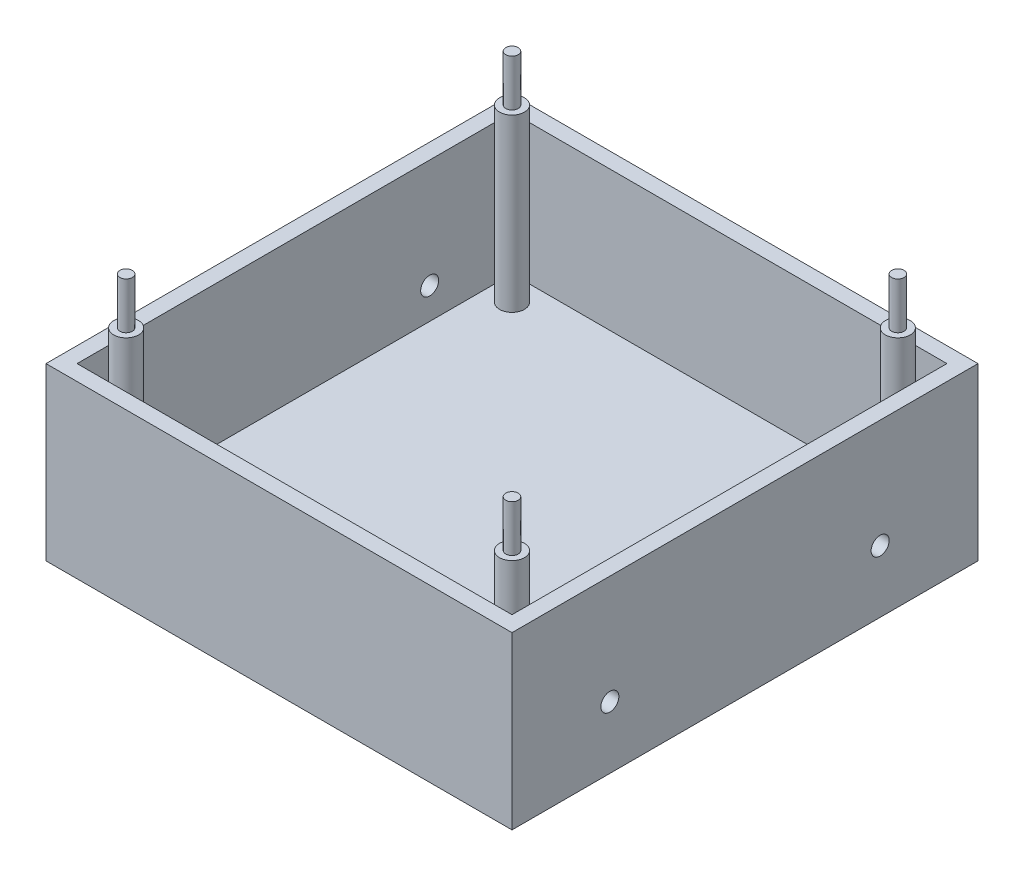
SolidWorks part; units mm, degrees
ref_plane "Front Plane" through (0, 0, 0) normal (0, 0, 1) x (1, 0, 0)
ref_plane "Top Plane" through (0, 0, 0) normal (0, 1, 0) x (1, 0, 0)
ref_plane "Right Plane" through (0, 0, 0) normal (1, 0, 0) x (0, 0, -1)
sketch "Sketch1" plane through (0, 0, 0) normal (0, 1, 0) x (1, 0, 0)
  line L0 (75, 0) -> (75, -156.3817) construction
  line L1 (0, 0) -> (150, 0)
  line L2 (0, 0) -> (0, -150)
  line L3 (0, -150) -> (150, -150)
  line L4 (150, 0) -> (150, -150)
  line L5 (0, -75) -> (163.2244, -75) construction
  line L7 (5, -5) -> (145, -5)
  line L8 (5, -5) -> (5, -145)
  line L9 (5, -145) -> (145, -145)
  line L10 (145, -5) -> (145, -145)
  line L11 (5, -5) -> (145, -145) construction
  line L12 (5, -145) -> (145, -5) construction
  circle A0 centre (12.9, -12.9) radius 4
  circle A1 centre (12.9, -12.9) radius 2
  circle A2 centre (137.1, -12.9) radius 2
  circle A3 centre (137.1, -12.9) radius 4
  circle A4 centre (137.1, -137.1) radius 2
  circle A5 centre (137.1, -137.1) radius 4
  circle A6 centre (12.9, -137.1) radius 2
  circle A7 centre (12.9, -137.1) radius 4
  point P9 (75, -75)
  point P29 (75, -75)
  dimension "D5" = 8
  dimension "D6" = 4
  dimension "D1" = 150
  dimension "D2" = 150
  dimension "D3" = 140
  dimension "D4" = 140
  dimension "D7" = 12.9
  dimension "D9" = 12.9
  dimension "D10" = 12.9
  dimension "D8" = 4
extrude "Boss-Extrude1" add sketch "Sketch1" along normal blind 55 contours L4 L1 L2 L3 L7 L10 L9 L8 region at (75, 0, 2.1213)
extrude "Boss-Extrude2" add sketch "Sketch1<3>" along normal blind 10 contours L10 L7 L8 L9 A7 A5 A3 A0 region at (75, 0, 75)
sketch "Sketch1<3>" plane through (0, 0, 0) normal (0, 1, 0) x (1, 0, 0) same geometry as "Sketch1"
extrude "Boss-Extrude3" add sketch "Sketch1<4>" along normal blind 65 contours A0 A1 | A3 A2 | A5 A4 | A7 A6 region at (9.0131, 0, 12.9) region at (133.2131, 0, 12.9) region at (133.2131, 0, 137.1) region at (9.0131, 0, 137.1)
sketch "Sketch1<4>" plane through (0, 0, 0) normal (0, 1, 0) x (1, 0, 0) same geometry as "Sketch1"
extrude "Boss-Extrude4" add sketch "Sketch1<5>" along normal blind 80 contours A6 | A4 | A2 | A1 region at (12.9, 0, 12.9) region at (137.1, 0, 12.9) region at (137.1, 0, 137.1) region at (12.9, 0, 137.1)
sketch "Sketch1<5>" plane through (0, 0, 0) normal (0, 1, 0) x (1, 0, 0) same geometry as "Sketch1"
sketch "Sketch3" plane through (0, 0, 0) normal (1, 0, 0) x (0, 0, -1)
  line L0 (0, 0) -> (-150, 0) construction
  line L1 (0, 55) -> (0, 0) construction
  line L2 (-150, 55) -> (-150, 0) construction
  circle A0 centre (-31.5, 20) radius 2.9
  circle A1 centre (-118.5, 20) radius 2.9
  dimension "D3" = 5.8
  dimension "D6" = 5.8
  dimension "D1" = 20
  dimension "D2" = 31.5
  dimension "D4" = 31.5
  dimension "D5" = 20
extrude "Cut-Extrude3" cut sketch "Sketch3" against normal blind 130 and the other way through all
